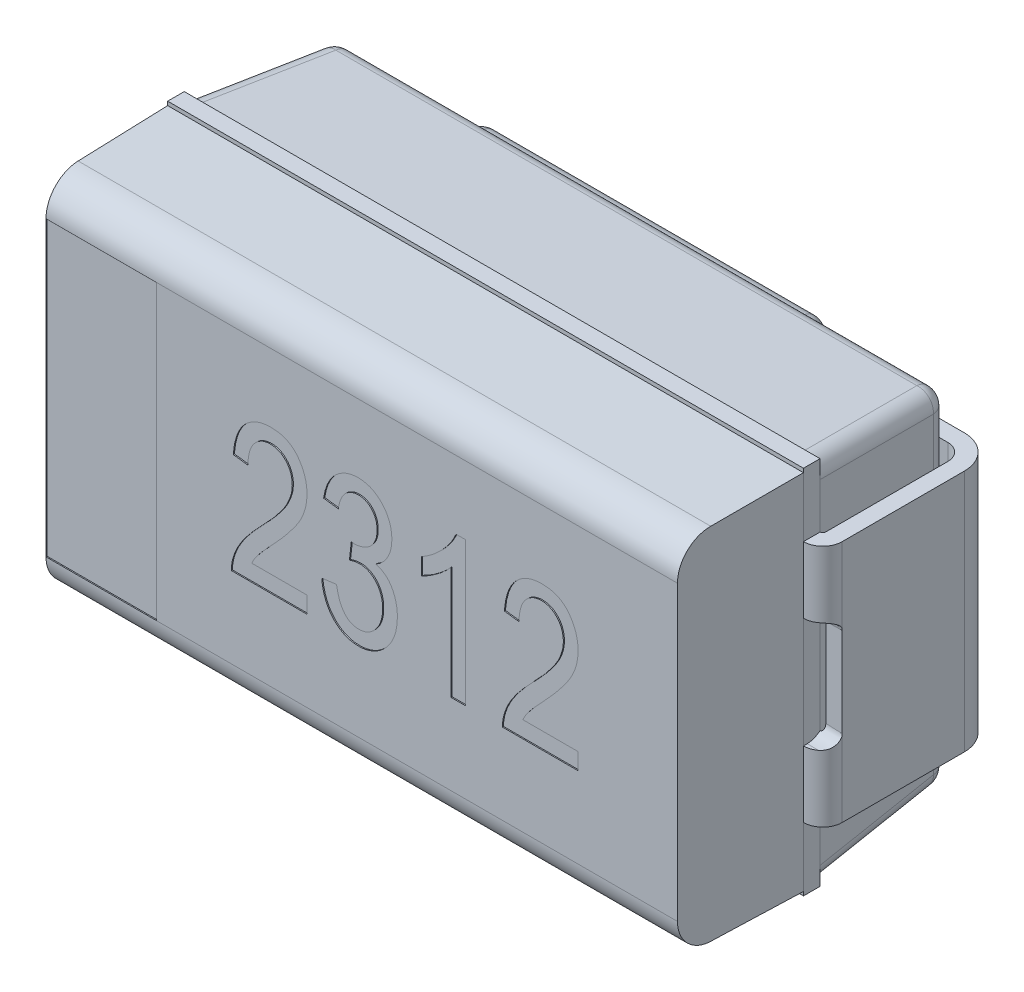
SolidWorks part; units mm, degrees
ref_plane "Front Plane" through (0, 0, 0) normal (0, 0, 1) x (1, 0, 0)
ref_plane "Top Plane" through (0, 0, 0) normal (0, 1, 0) x (1, 0, 0)
ref_plane "Right Plane" through (0, 0, 0) normal (1, 0, 0) x (0, 0, -1)
sketch "Sketch1" plane through (0, 0, 0) normal (0, 0, 1) x (1, 0, 0)
  line L1 (-2.875, 1.66) -> (2.875, 1.66)
  line L2 (-2.875, 1.66) -> (-2.875, -1.66)
  line L3 (-2.875, -1.66) -> (2.875, -1.66)
  line L4 (2.875, 1.66) -> (2.875, -1.66)
  line L5 (-2.875, 1.66) -> (2.875, -1.66) construction
  line L6 (-2.875, -1.66) -> (2.875, 1.66) construction
  point P0 (0, 0)
  dimension "D1" = 3.32
  dimension "D2" = 5.75
extrude "Boss-Extrude1" add sketch "Sketch1" against normal blind 1.26 draft 5 from offset 1.43 contours L2 L3 L4 L1
fillet "Fillet2" radius 0.15 8 edges at (-2.7648, 0, 0.17) (0, -1.5498, 0.17) (2.7648, 0, 0.17) (0, 1.5498, 0.17) (2.8199, 1.6049, 0.8) (-2.8199, 1.6049, 0.8) (2.8199, -1.6049, 0.8) (-2.8199, -1.6049, 0.8)
sketch "Sketch3" plane through (0, 0, 1.43) normal (0, 0, 1) x (1, 0, 0)
  line L0 (2.875, 1.5106) -> (2.875, -1.5106) construction
  line L1 (-2.875, 1.675) -> (2.875, 1.675)
  line L2 (-2.875, 1.675) -> (-2.875, -1.675)
  line L3 (-2.875, -1.675) -> (2.875, -1.675)
  line L4 (2.875, 1.675) -> (2.875, -1.675)
  line L5 (-2.875, 1.675) -> (2.875, -1.675) construction
  line L6 (-2.875, -1.675) -> (2.875, 1.675) construction
  point P0 (0, 0)
  dimension "D1" = 3.35
extrude "Boss-Extrude2" add sketch "Sketch3" along normal blind 0.15
sketch "Sketch4" plane through (0, 0, 1.58) normal (0, 0, 1) x (1, 0, 0)
  line L0 (2.875, -1.675) -> (2.875, 1.675) construction
  line L1 (-2.875, 1.64) -> (2.875, 1.64)
  line L2 (-2.875, 1.64) -> (-2.875, -1.64)
  line L3 (-2.875, -1.64) -> (2.875, -1.64)
  line L4 (2.875, 1.64) -> (2.875, -1.64)
  line L5 (-2.875, 1.64) -> (2.875, -1.64) construction
  line L6 (-2.875, -1.64) -> (2.875, 1.64) construction
  point P0 (0, 0)
  dimension "D1" = 3.28
extrude "Boss-Extrude4" add sketch "Sketch4" along normal blind 1.12 draft 1
fillet "Fillet4" radius 0.3012 2 edges at (0, -1.6205, 2.7) (0, 1.6205, 2.7)
sketch "Sketch5" plane through (0, 0, 0.17) normal (0, 0, -1) x (-1, 0, 0)
  line L1 (-1.6, 1.45) -> (1.6, 1.45)
  line L2 (-1.6, 1.45) -> (-1.6, -1.45)
  line L3 (-1.6, -1.45) -> (1.6, -1.45)
  line L4 (1.6, 1.45) -> (1.6, -1.45)
  line L5 (-1.6, 1.45) -> (1.6, -1.45) construction
  line L6 (-1.6, -1.45) -> (1.6, 1.45) construction
  point P0 (0, 0)
  dimension "D1" = 3.2
  dimension "D2" = 2.9
extrude "Boss-Extrude5" add sketch "Sketch5" along normal blind 0.16 from offset 0.01 offset against normal yes
fillet "Fillet5" radius 0.15 8 edges at (0, -1.45, 0.02) (1.6, 0, 0.02) (0, 1.45, 0.02) (-1.6, 0, 0.02) (-1.6, 1.45, 0.0974) (-1.6, -1.45, 0.0974) (1.6, 1.45, 0.0974) (1.6, -1.45, 0.0974)
sketch "Sketch7" plane through (0, 0, 0) normal (0, 1, 0) x (1, 0, 0)
  line L0 (2.875, -1.58) -> (2.875, -1.43)
  line L1 (2.9, -1.405) -> (2.9, -0.3)
  line L2 (2.75, -0.15) -> (1.779, -0.15)
  line L3 (1.779, -0.15) -> (1.779, 0)
  line L4 (1.779, 0) -> (2.75, 0)
  line L5 (3.05, -0.3) -> (3.05, -1.405)
  line L7 (2.6273, -0.17) -> (1.5494, -0.17) construction
  line L8 (0, 0) -> (0, -2.7) construction
  line L9 (-2.8555, -2.7) -> (2.8555, -2.7) construction
  line L10 (-3.05, -0.3) -> (-3.05, -1.405)
  line L11 (-1.779, 0) -> (-2.75, 0)
  line L12 (-1.779, -0.15) -> (-1.779, 0)
  line L13 (-2.75, -0.15) -> (-1.779, -0.15)
  line L14 (-2.9, -1.405) -> (-2.9, -0.3)
  line L15 (-2.875, -1.58) -> (-2.875, -1.43)
  arc A0 (2.875, -1.43) -> (2.9, -1.405) centre (2.875, -1.405) ccw
  arc A1 (2.9, -0.3) -> (2.75, -0.15) centre (2.75, -0.3) ccw
  arc A2 (2.75, 0) -> (3.05, -0.3) centre (2.75, -0.3) cw
  arc A3 (3.05, -1.405) -> (2.875, -1.58) centre (2.875, -1.405) cw
  arc A4 (-3.05, -1.405) -> (-2.875, -1.58) centre (-2.875, -1.405) ccw
  arc A5 (-2.75, 0) -> (-3.05, -0.3) centre (-2.75, -0.3) ccw
  arc A6 (-2.9, -0.3) -> (-2.75, -0.15) centre (-2.75, -0.3) cw
  arc A7 (-2.875, -1.43) -> (-2.9, -1.405) centre (-2.875, -1.405) cw
  dimension "D5" = 0.3
  dimension "D1" = 0.02
  dimension "D2" = 0.15
  dimension "D3" = 1.271
  dimension "D4" = 3.05
extrude "Boss-Extrude6" add sketch "Sketch7" along normal mid plane 2.2
sketch "Sketch9" plane through (-2.875, 0, 0) normal (-1, 0, 0) x (0, 0, 1)
  line L0 (1.58, 0.6867) -> (1.58, -0.6867)
  line L3 (0, 0) -> (2.7, 0) construction
  line L4 (2.7, 1.3245) -> (2.7, -1.3245) construction
  line L8 (0.7238, 0.4) -> (0.7238, -0.4)
  line L9 (0.8446, -0.5471) -> (1.3816, -0.6535)
  line L10 (1.3816, 0.6535) -> (0.8446, 0.5471)
  arc A2 (0.7238, -0.4) -> (0.8446, -0.5471) centre (0.8738, -0.4) ccw
  arc A3 (0.8446, 0.5471) -> (0.7238, 0.4) centre (0.8738, 0.4) ccw
  spline S2 degree 3 poles (1.58, -0.6867) (1.574, -0.6811) (1.55, -0.6756) (1.4777, -0.6645) (1.4298, -0.659) (1.3816, -0.6535) knots 0 0 0 0 0.5 0.5 1 1 1 1
  spline S3 degree 3 poles (1.58, 0.6867) (1.5792, 0.6859) (1.5767, 0.6843) (1.5707, 0.6818) (1.5621, 0.6792) (1.5513, 0.6767) (1.5383, 0.6741) (1.5233, 0.6715) (1.5065, 0.6689) (1.4882, 0.6664) (1.4685, 0.6638) (1.4478, 0.6612) (1.4262, 0.6586) (1.404, 0.656) (1.389, 0.6543) (1.3816, 0.6535) knots 0.004713 0.004713 0.004713 0.004713 0.008438 0.012657 0.016876 0.021095 0.025314 0.029533 0.033751 0.03797 0.042189 0.046408 0.050627 0.054846 0.059065 0.059065 0.059065 0.059065
extrude "Cut-Extrude2" cut sketch "Sketch9" along normal blind 2.4
sketch "Sketch12" plane through (2.875, 0, 0) normal (1, 0, 0) x (0, 0, -1)
  line L0 (-1.58, 0.5) -> (-1.58, -0.5)
  line L1 (0, 0) -> (-2.7, 0) construction
  line L2 (-2.7, -1.3245) -> (-2.7, 1.3245) construction
  line L3 (-1.5462, -0.5) -> (-1.58, -0.5)
  line L4 (-1.4026, 0.4) -> (-1.4026, -0.4)
  line L5 (-1.58, 0.5) -> (-1.5462, 0.5)
  spline S2 degree 3 poles (-1.4026, -0.4) (-1.4033, -0.4073) (-1.4048, -0.4222) (-1.4169, -0.4428) (-1.4354, -0.4607) (-1.4656, -0.48) (-1.5077, -0.4969) (-1.533, -0.4989) (-1.5462, -0.5) knots 0 0 0 0 0.100894 0.204467 0.32118 0.458503 0.717255 1 1 1 1
  spline S3 degree 3 poles (-1.5462, 0.5) (-1.5375, 0.4995) (-1.5206, 0.4985) (-1.489, 0.4897) (-1.4571, 0.4751) (-1.4284, 0.4557) (-1.4066, 0.4298) (-1.4039, 0.4097) (-1.4026, 0.4) knots 0 0 0 0 0.195151 0.376782 0.549697 0.724506 0.867709 1 1 1 1
extrude "Cut-Extrude4" cut sketch "Sketch12" along normal up to next
sketch "Sketch13" plane through (0, 0, 2.7) normal (0, 0, 1) x (1, 0, 0)
  line L0 (2.8555, 1.3245) -> (-2.8555, 1.3245) construction
  line L1 (-2.8555, -1.3245) -> (-1.8555, -1.3245)
  line L2 (-2.8555, -1.3245) -> (-2.8555, 1.3245)
  line L3 (-2.8555, 1.3245) -> (-1.8555, 1.3245)
  line L4 (-1.8555, -1.3245) -> (-1.8555, 1.3245)
  dimension "D1" = 1
extrude "Cut-Extrude5" cut sketch "Sketch13" against normal blind 0.01
sketch "Sketch16" plane through (0, 0, 2.7) normal (0, 0, 1) x (1, 0, 0)
  line L0 (-1.2454, -0.5936) -> (2.2455, -0.5936) construction
  text T0 "2312\r\n" font "Arial Narrow" height in points 5
extrude "Cut-Extrude6" cut sketch "Sketch16" against normal blind 0.01
